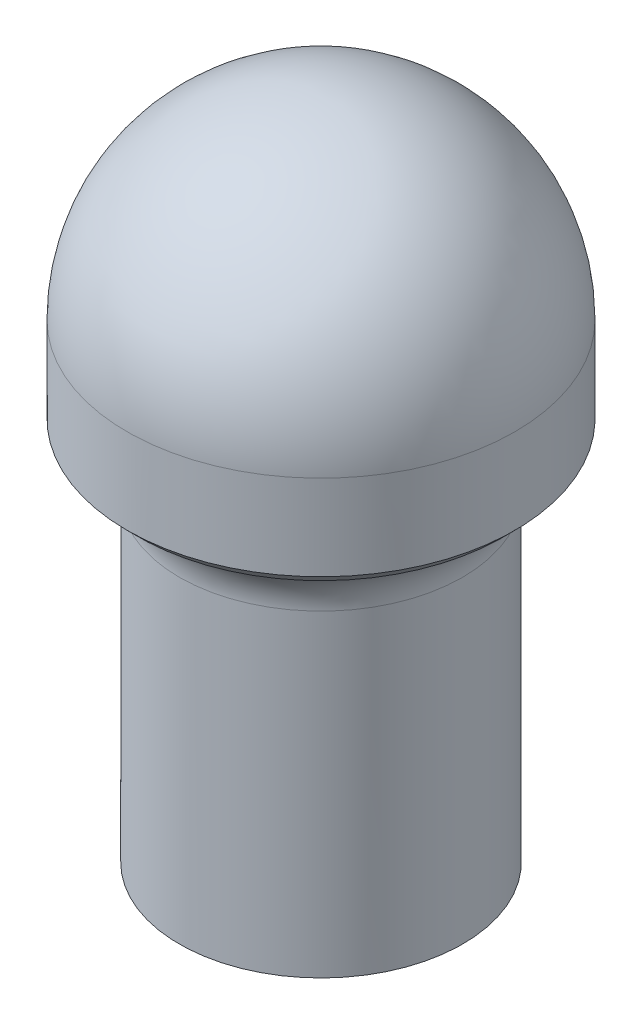
SolidWorks part; units mm, degrees
material "6061-T6 (SS)"
ref_plane "Front Plane" through (0, 0, 0) normal (0, 0, 1) x (1, 0, 0)
ref_plane "Top Plane" through (0, 0, 0) normal (0, 1, 0) x (1, 0, 0)
ref_plane "Right Plane" through (0, 0, 0) normal (1, 0, 0) x (0, 0, -1)
sketch "Sketch1" plane through (0, 0, 0) normal (0, 0, 1) x (1, 0, 0)
  line L0 (0, 25.4) -> (0, 43.6626) construction
  line L2 (4.8966, 14.7066) -> (-5.3865, 14.7066) construction
  line L3 (-5.334, 38.3286) -> (-5.334, 35.7251)
  line L4 (-5.334, 35.7251) -> (-3.899, 35.7251)
  line L5 (-3.899, 35.7251) -> (-3.899, 25.4)
  line L6 (-3.899, 25.4) -> (0, 25.4)
  line L7 (0, 25.4) -> (0, 43.6626)
  arc A0 (0, 43.6626) -> (-5.334, 38.3286) centre (0, 38.3286) ccw
  point P2 (0, 0)
  point P8 (0, 0)
  dimension "D2" = 10.668
  dimension "D1" = 28.956
  dimension "D3" = 7.798
  dimension "D4" = 18.2626
  dimension "D5" = 7.9375
revolve "Revolve1" add sketch "Sketch1" angle 360 about L0
fillet "Fillet1" radius 1.5875 1 edges at (0, 35.7251, -3.899)
chamfer "Chamfer2" distance 0.254 angle 45 1 edges at (0, 35.7251, -5.334) first distance on face at (0, 35.7251, -5.334)
hole_wizard "M7x1.0 Tapped Hole1" positions "Sketch2" profile "Sketch3" tap size "M7x1.0" standard "ANSI Metric"
sketch "Sketch2" plane through (0, 25.4, 0) normal (0, -1, 0) x (-1, 0, 0)
  point P0 (0, 0)
sketch "Sketch3" plane through (0, 25.4, 0) normal (1, 0, 0) x (0, 0, -1)
  line L0 (0, 0) -> (0, 17.8046)
  line L1 (0, 17.8046) -> (3, 16.002)
  line L2 (3, 16.002) -> (3, 0)
  line L5 (3, 0) -> (0, 0)
  line L10 (0, 17.8046) -> (-3, 16.002) construction
  line L11 (0, -6.35) -> (0, 107.95) construction
  dimension "Tap Drill Dia." = 6
  dimension "Tap Drill Depth" = 16.002
  dimension "Drill Angle" = 118
cosmetic thread "Hole Thread1" parameters "D1"=9.906, "D2"=7
sketch "Sketch4" plane through (0, 25.4, 0) normal (0, -1, 0) x (1, 0, 0)
  circle A0 centre (0, 0) radius 3.5
  dimension "D1" = 7
extrude "Cut-Extrude1" cut sketch "Sketch4" against normal blind 2.5
